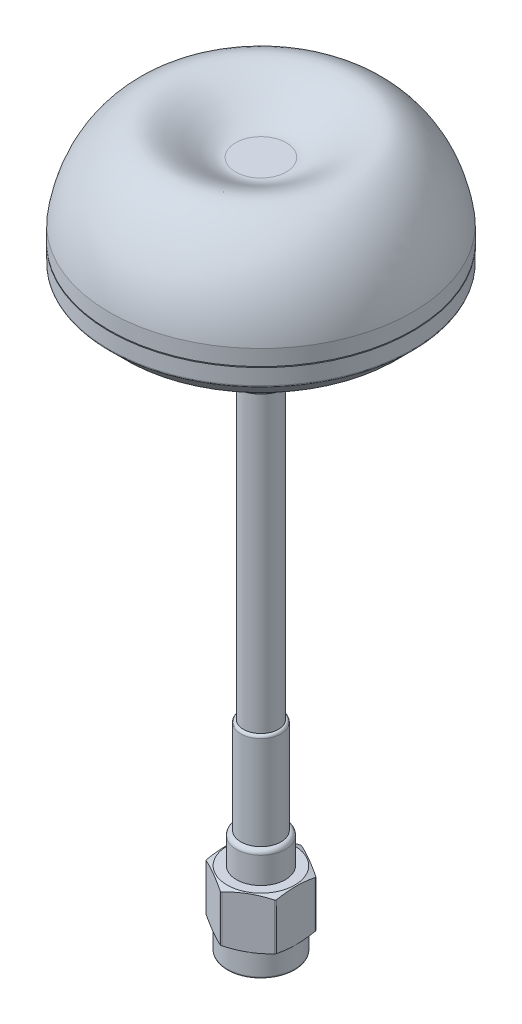
SolidWorks part; units mm, degrees
ref_plane "Front Plane" through (0, 0, 0) normal (0, 0, 1) x (1, 0, 0)
ref_plane "Top Plane" through (0, 0, 0) normal (0, 1, 0) x (1, 0, 0)
ref_plane "Right Plane" through (0, 0, 0) normal (1, 0, 0) x (0, 0, -1)
sketch "Sketch1" plane through (0, 0, 0) normal (0, 1, 0) x (1, 0, 0)
  circle A0 centre (0, 0) radius 3.88
  dimension "D1" = 7.76
extrude "Boss-Extrude1" add sketch "Sketch1" along normal blind 2.6
ref_axis "Axis1" through (0, 2.6, 0) along (0, -1, 0)
sketch "Sketch2" plane through (0, 2.6, 0) normal (0, 1, 0) x (1, 0, 0)
  line L1 (0, -4.6188) -> (4, -2.3094)
  line L2 (4, -2.3094) -> (4, 2.3094)
  line L3 (4, 2.3094) -> (0, 4.6188)
  line L4 (0, 4.6188) -> (-4, 2.3094)
  line L5 (-4, 2.3094) -> (-4, -2.3094)
  line L6 (-4, -2.3094) -> (0, -4.6188)
  circle A0 centre (0, 0) radius 4 construction
  dimension "D1" = 8
extrude "Boss-Extrude2" add sketch "Sketch2" along normal blind 5.9
sketch "Sketch3" plane through (0, 0, 0) normal (0, -1, 0) x (1, 0, 0)
  circle A0 centre (0, 0) radius 3.25
  dimension "D1" = 6.5
extrude "Cut-Extrude1" cut sketch "Sketch3" against normal blind 1
sketch "Sketch4" plane through (0, 1, 0) normal (0, -1, 0) x (1, 0, 0)
  circle A0 centre (0, 0) radius 2.85
  circle A1 centre (0, 0) radius 0.475
  dimension "D1" = 5.7
  dimension "D2" = 0.95
extrude "Cut-Extrude2" cut sketch "Sketch4" against normal blind 2.45
sketch "Sketch5" plane through (0, 3.45, 0) normal (0, -1, 0) x (1, 0, 0)
  circle A0 centre (0, 0) radius 2.6
  circle A1 centre (0, 0) radius 2.85
  circle A2 centre (0, 0) radius 2.85
  dimension "D2" = 0.25
  dimension "D1" = 0
extrude "Cut-Extrude3" cut sketch "Sketch5" against normal blind 4
sketch "Sketch6" plane through (0, 3.45, 0) normal (0, -1, 0) x (1, 0, 0)
  circle A0 centre (0, 0) radius 0.475 construction
  circle A1 centre (0, 0) radius 0.475
  circle A4 centre (0, 0) radius 2.5
  circle A5 centre (0, 0) radius 2.5
  dimension "D1" = 0.1
extrude "Cut-Extrude4" cut sketch "Sketch6" against normal blind 0.1
thread "Thread1" pitch 1 method cut profile "Thread Profile1" start angle 0, offset 1, length 0, pitch 1, diameter 5.7
ref_plane "Plane1" through (2.85, 0, 0) normal (0, 0, 1) x (1, 0, 0)
sketch "Thread Profile1" plane through (2.85, 0, 0) normal (0, 0, 1) x (1, 0, 0)
  line L0 (0, 0) -> (0, 1) construction
  line L1 (0, 0) -> (0.5413, 0.3125)
  line L2 (0.5413, 0.3125) -> (0.5413, 0.4375)
  line L3 (0.5413, 0.4375) -> (0, 0.75)
  line L4 (0.5413, 0.375) -> (0, 0.375) construction
  line L11 (0, 0) -> (0, 0.75)
  point P2 (0, 0)
  dimension "Pitch" = 1
  dimension "Profile_Angle" = 60
  dimension "Profile_Land" = 0.125
  dimension "Profile_Height" = 0.5413
chamfer "Chamfer1" distance 1 angle 20 1 edges at (0, 1, -0.475) first distance on face at (0, 1, -0.475)
ref_plane "Plane2" through (0, 0, 0) normal (-0.5, 0, 0.866) x (0.866, 0, 0.5)
sketch "Sketch10" plane through (0, 0, 0) normal (-0.5, 0, 0.866) x (0.866, 0, 0.5)
  line L0 (-3.8688, 8.5) -> (-4.6188, 8.2)
  line L1 (-4.6188, 8.5) -> (-2.3094, 8.5) construction
  line L2 (-4.6188, 8.5) -> (-4.6188, 2.6) construction
  line L3 (-4.6188, 8.2) -> (-4.6188, 8.5)
  line L4 (-4.6188, 8.5) -> (-3.8688, 8.5)
  line L5 (-4.6188, 5.55) -> (4.6188, 5.55) construction
  line L6 (4.6188, 8.5) -> (4.6188, 2.6) construction
  line L7 (-4.6188, 2.9) -> (-4.6188, 2.6)
  line L8 (-3.8688, 2.6) -> (-4.6188, 2.9)
  line L9 (-4.6188, 2.6) -> (-3.8688, 2.6)
  dimension "D1" = 0.75
  dimension "D2" = 0.3
revolve "Cut-Revolve1" cut sketch "Sketch10" angle 360 about axis through (0, 2.6, 0) along (0, -1, 0)
fillet "Fillet1" radius 0.2 8 edges at (4, 5.55, -2.3094) (0, 5.55, -4.6188) (-4, 5.55, -2.3094) (0, 0, -3.25) (0, 0, 3.88) (4, 5.55, 2.3094) (0, 5.55, 4.6188) (-4, 5.55, 2.3094)
sketch "Sketch11" plane through (0, 8.5, 0) normal (0, 1, 0) x (1, 0, 0)
  circle A0 centre (0, 0) radius 2.8
  dimension "D1" = 5.6
extrude "Boss-Extrude3" add sketch "Sketch11" along normal blind 3.5
sketch "Sketch12" plane through (0, 12, 0) normal (0, 1, 0) x (1, 0, 0)
  circle A0 centre (0, 0) radius 2.3
  dimension "D1" = 4.6
extrude "Boss-Extrude4" add sketch "Sketch12" along normal blind 11
sketch "Sketch13" plane through (0, 23, 0) normal (0, 1, 0) x (1, 0, 0)
  circle A0 centre (0, 0) radius 2
  dimension "D1" = 4
extrude "Boss-Extrude6" add sketch "Sketch13" along normal offset from surface (34.5 mm away) 49 up to face at (0, 8.5, 2.8) offset beyond the face yes
fillet "Fillet2" radius 0.5 1 edges at (0, 12, 2.8)
fillet "Fillet3" radius 0.3 1 edges at (0, 23, 2.3)
sketch "Sketch15" plane through (0, 0, 0) normal (0, 0, 1) x (1, 0, 0)
  line L0 (0, 57.5) -> (0, 81.8) construction
  line L1 (2, 57.5) -> (-2, 57.5) construction
  line L2 (-2, 57.5) -> (-3.375, 57.5)
  line L3 (-3.375, 57.5) -> (-3.375, 66.22)
  line L4 (-3.375, 66.22) -> (-15.35, 66.22)
  line L5 (-15.35, 66.22) -> (-17.35, 68.22)
  line L6 (-5.0104, 78.7) -> (6.43, 78.7) construction
  line L7 (0, 78.7) -> (-2.9, 78.7)
  line L8 (-10.9735, 81.8) -> (6.668, 81.8) construction
  line L9 (-10, 81.8) -> (-10, 78.7) construction
  line L10 (0, 78.7) -> (0, 57.5)
  line L11 (-17.35, 68.22) -> (-17.35, 72.02)
  line L12 (-2, 57.5) -> (0, 57.5)
  spline S0 degree 3 poles (-2.9, 78.7) (-4.4832, 78.6616) (-7.1859, 81.4827) (-12.0319, 82.0994) (-16.5701, 77.9286) (-17.35, 72.02) knots 0 0 0 0 0.507969 0.607969 1 1 1 1
  dimension "D1" = 24.3
  dimension "D2" = 6.75
  dimension "D3" = 8.72
  dimension "D4" = 34.7
  dimension "D5" = 135
  dimension "D6" = 2
  dimension "D7" = 3.1
  dimension "D8" = 5.8
  dimension "D9" = 10
  dimension "D10" = 3.8
revolve "Revolve1" add sketch "Sketch15" angle 360 about axis through (0, 2.6, 0) along (0, -1, 0)
fillet "Fillet4" radius 3 1 edges at (0, 66.22, 3.375)
fillet "Fillet5" radius 0.25 3 edges at (0, 68.22, 17.35) (0, 66.22, 15.35) (0, 57.5, 3.375)
sketch "Sketch16" plane through (0, 0, 0) normal (0, 0, 1) x (1, 0, 0)
  line L0 (-17.35, 72.02) -> (-17.35, 68.3236) construction
  line L1 (-17.35, 72.02) -> (-17.35, 68.3236)
  line L2 (-17.35, 70.1718) -> (17.35, 70.1718) construction
  line L3 (17.35, 68.3236) -> (17.35, 72.02) construction
  line L4 (-17.15, 70.1718) -> (-17.35, 70.1718) construction
  line L5 (-17.35, 70.2218) -> (-17.15, 70.2218)
  line L6 (-17.35, 70.2218) -> (-17.35, 70.1218)
  line L7 (-17.35, 70.1218) -> (-17.15, 70.1218)
  line L8 (-17.15, 70.2218) -> (-17.15, 70.1218)
  dimension "D1" = 0.1
  dimension "D2" = 0.2
revolve "Cut-Revolve2" cut sketch "Sketch16" angle 360 about axis through (0, 2.6, 0) along (0, -1, 0) region at (-17.25, 70.1718, 0)
